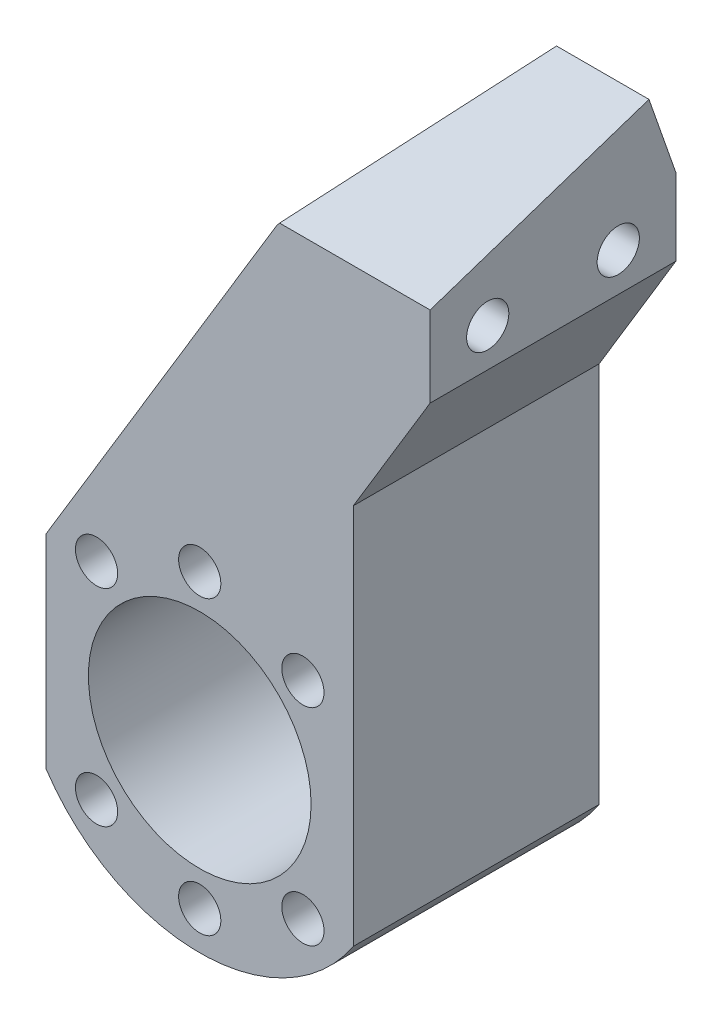
SolidWorks part; units mm, degrees
ref_plane "Plan de face" through (0, 0, 0) normal (0, 0, 1) x (1, 0, 0)
ref_plane "Plan de dessus" through (0, 0, 0) normal (0, 1, 0) x (1, 0, 0)
ref_plane "Plan de droite" through (0, 0, 0) normal (1, 0, 0) x (0, 0, -1)
sketch "Esquisse2" plane through (0, 0, 0) normal (0, 0, 1) x (1, 0, 0)
  line L0 (20, 13.2665) -> (20, -13.2665)
  line L1 (-20, 13.2665) -> (-20, -13.2665)
  line L2 (-20, 0) -> (20, 0) construction
  arc A2 (-20, 13.2665) -> (20, 13.2665) centre (0, 0) cw
  arc A3 (-20, -13.2665) -> (20, -13.2665) centre (0, 0) ccw
  circle A4 centre (0, 0) radius 19 construction
  circle A5 centre (0, 19) radius 2.75
  circle A6 centre (-13.435, 13.435) radius 2.75
  circle A7 centre (13.435, 13.435) radius 2.75
  circle A8 centre (0, -19) radius 2.75
  circle A9 centre (13.435, -13.435) radius 2.75
  circle A10 centre (-13.435, -13.435) radius 2.75
  circle A11 centre (0, 0) radius 14.5
  point P4 (0, 0)
  point P10 (-20, 0)
  point P11 (20, 0)
  dimension "D2" = 24
  dimension "D3" = 38
  dimension "D4" = 5.5
  dimension "D5" = 29
  dimension "D1" = 40
  dimension "D6" = 45
  dimension "D7" = 45
  dimension "D8" = 45
  dimension "D9" = 45
extrude "Boss.-Extru.1" add sketch "Esquisse2" along normal blind 32
sketch "Esquisse7" plane through (0, 0, 0) normal (0, 0, -1) x (-1, 0, 0)
  line L2 (-10, 63.001) -> (20, 13.2665)
  line L3 (-10, 63.001) -> (-30, 63.001)
  line L4 (-30, 63.001) -> (-30, 53.001)
  line L6 (-20, 13.2665) -> (-20, 36.4228)
  line L7 (-20, 36.4228) -> (-30, 53.001)
  arc A0 (20, 13.2665) -> (-20, 13.2665) centre (0, 0) ccw construction
  arc A1 (20, 13.2665) -> (-20, 13.2665) centre (0, 0) ccw
  dimension "D1" = 39.7345
  dimension "D2" = 10
  dimension "D3" = 10
  dimension "D4" = 20
extrude "Boss.-Extru.4" add sketch "Esquisse7" against normal up to surface (32 mm away) up to face at (0, 0, 32)
sketch "Esquisse10" plane through (30, 0, 0) normal (1, 0, 0) x (0, 0, -1)
  line L0 (-32, 53.001) -> (-32, 63.001) construction
  line L1 (-24.5, 58.001) -> (-7.5, 58.001) construction
  line L2 (-32, 63.001) -> (0, 63.001) construction
  circle A0 centre (-24.5, 58.001) radius 2.75
  circle A1 centre (-7.5, 58.001) radius 2.75
  point P4 (-16, 58.001)
  point P7 (-32, 58.001)
  point P10 (-16, 63.001)
  dimension "D1" = 5.5
  dimension "D2" = 7.5
extrude "Enlèv. mat.-Extru.3" cut sketch "Esquisse10" against normal up to next
sketch "Esquisse11" plane through (30, 0, 0) normal (1, 0, 0) x (0, 0, -1)
  line L0 (-32, 63.001) -> (0, 63.001)
  line L4 (0, 63.001) -> (-3.5, 73.001)
  line L5 (-32, 63.001) -> (-32, 63.501)
  line L6 (-32, 63.501) -> (-3.5, 73.001)
  dimension "D1" = 10
  dimension "D2" = 3.5
  dimension "D3" = 0.5
extrude "Boss.-Extru.6" add sketch "Esquisse11" against normal up to vertex (20 mm away) up to point (10, 63.001, 32)
sketch "Esquisse12" plane through (0, 0, 0) normal (0, 0, -1) x (-1, 0, 0)
  line L0 (-10, 63.001) -> (-17.9628, 73.001)
  line L1 (-10, 63.001) -> (-10, 73.001) construction
  line L4 (-10, 63.001) -> (-10, 73.001)
  line L6 (-17.9628, 73.001) -> (-10, 73.001)
  line L7 (-10, 73.001) -> (-30, 73.001) construction
extrude "Enlèv. mat.-Extru.4" cut sketch "Esquisse12" against normal up to next
ref_plane "Plan1" through (20, 0, 0) normal (1, 0, 0) x (0, 0, -1)
sketch "Esquisse13" plane through (20, 0, 0) normal (1, 0, 0) x (0, 0, -1)
  circle A0 centre (-7.5, 58.001) radius 6
  circle A1 centre (-24.5, 58.001) radius 6
  dimension "D1" = 12
extrude "Enlèv. mat.-Extru.5" cut sketch "Esquisse13" against normal up to next
